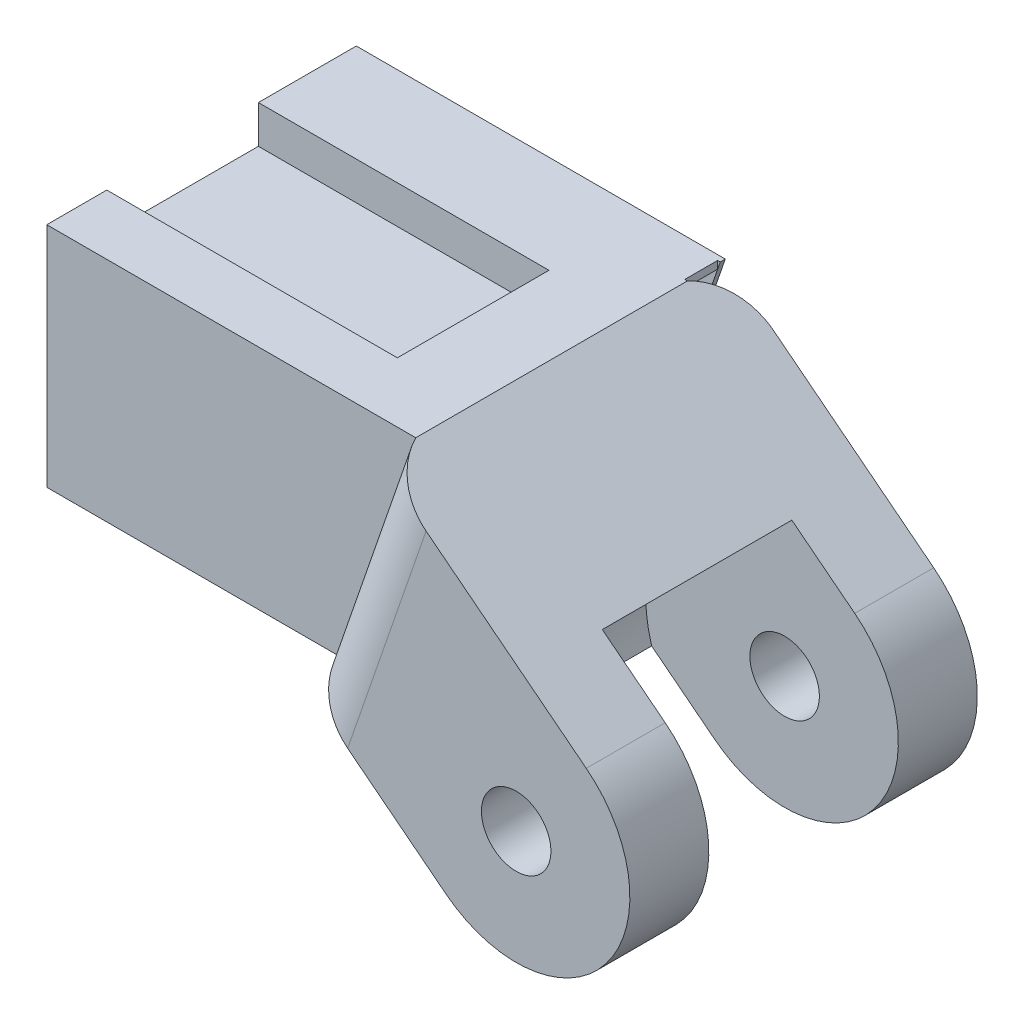
SolidWorks part; units mm, degrees
ref_plane "Front Plane" through (0, 0, 0) normal (0, 0, 1) x (1, 0, 0)
ref_plane "Top Plane" through (0, 0, 0) normal (0, 1, 0) x (1, 0, 0)
ref_plane "Right Plane" through (0, 0, 0) normal (1, 0, 0) x (0, 0, -1)
ref_plane "Plane1" through (0, 0, 10.75) normal (0, 0, 1) x (1, 0, 0)
sketch "Sketch1" plane through (0, 0, 0) normal (0, 0, 1) x (1, 0, 0)
  line L0 (-40.1551, -0.8363) -> (-17.1551, -0.8363)
  line L1 (-17.1551, -0.8363) -> (-5.5478, -9.923)
  line L2 (-40.1551, -0.8363) -> (-40.1551, 17.1637)
  line L3 (-40.1551, 17.1637) -> (-10.9475, 17.1637)
  line L4 (-10.9475, 17.1637) -> (5.5478, 4.2505)
  line L5 (-5.5478, -9.923) -> (5.5478, 4.2505) construction
  arc A1 (-5.5478, -9.923) -> (5.5478, 4.2505) centre (0, -2.8363) ccw
  dimension "D3" = 23
  dimension "D1" = 18
  dimension "D2" = 18
  dimension "D4" = 20
extrude "Boss-Extrude1" add sketch "Sketch1" along normal blind 5
sketch "Sketch14" plane through (0, 0, 5) normal (0, 0, 1) x (1, 0, 0)
  line L0 (-40.1551, -0.8363) -> (-40.1551, 17.1637)
  line L1 (-40.1551, 17.1637) -> (-10.9475, 17.1637)
  line L2 (-5.5478, -9.923) -> (-17.1551, -0.8363)
  line L3 (-10.9475, 17.1637) -> (-40.1551, 17.1637) construction
  line L7 (-17.1551, -0.8363) -> (-40.1551, -0.8363)
  line L8 (-10.9475, 17.1637) -> (5.5478, 4.2505)
  arc A1 (-5.5478, -9.923) -> (5.5478, 4.2505) centre (0, -2.8363) ccw construction
  arc A2 (-5.5478, -9.923) -> (5.5478, 4.2505) centre (0, -2.8363) ccw
extrude "Boss-Extrude7" add sketch "Sketch14" along normal blind 5.75 contours L2 L7 L0 L1 L8 A2
sketch "Sketch27" plane through (0, 0, 0) normal (0, 0, 1) x (1, 0, 0)
  line L0 (-17.1551, -0.8363) -> (-10.9475, 17.1637)
  line L1 (-10.9475, 17.1637) -> (5.5478, 4.2505)
  line L2 (-17.1551, -0.8363) -> (-5.5478, -9.923)
  arc A0 (-5.5478, -9.923) -> (5.5478, 4.2505) centre (0, -2.8363) ccw
  arc A1 (-5.5478, -9.923) -> (5.5478, 4.2505) centre (0, -2.8363) ccw construction
extrude "Boss-Extrude8" add sketch "Sketch27" against normal blind 3
sketch "Sketch15" plane through (0, 0, -3) normal (0, 0, -1) x (-1, 0, 0)
  circle A0 centre (0, -2.8363) radius 2.75
  arc A1 (-5.5478, 4.2505) -> (5.5478, -9.923) centre (0, -2.8363) ccw construction
  dimension "D1" = 5.5
extrude "Cut-Extrude7" cut sketch "Sketch15" against normal through all
fillet "Fillet2" radius 5 1 edges at (-14.0513, 8.1637, -3)
mirror "Mirror1" about plane through (0, -2.8363, 10.75) normal (0, 0, 1) of bodies 117 114
sketch "Sketch16" plane through (-40.1551, 0, 0) normal (-1, 0, 0) x (0, 0, 1)
  line L0 (21.5, -0.8363) -> (0, -0.8363) construction
  line L1 (4.75, -0.8363) -> (16.75, -0.8363)
  line L2 (4.75, -0.8363) -> (4.75, 2.1637)
  line L3 (4.75, 2.1637) -> (16.75, 2.1637)
  line L4 (16.75, -0.8363) -> (16.75, 2.1637)
  line L6 (21.5, 17.1637) -> (0, 17.1637) construction
  line L8 (16.75, 17.1637) -> (4.75, 17.1637)
  line L9 (16.75, 17.1637) -> (16.75, 14.1637)
  line L11 (16.75, 14.1637) -> (4.75, 14.1637)
  line L12 (4.75, 17.1637) -> (4.75, 14.1637)
  point P7 (10.75, 17.1637)
  dimension "D1" = 12
  dimension "D2" = 3
extrude "Cut-Extrude8" cut sketch "Sketch16" against normal blind 23
sketch "Sketch17" plane through (-40.1551, 0, 0) normal (-1, 0, 0) x (0, 0, 1)
  line L0 (21.5, -0.8363) -> (16.75, -0.8363) construction
  line L1 (21.5, 17.1637) -> (21.5, -0.8363) construction
  circle A0 centre (10.75, 8.1637) radius 2.35
  dimension "D1" = 4.7
  dimension "D2" = 9
  dimension "D3" = 10.75
extrude "Cut-Extrude9" cut sketch "Sketch17" against normal blind 32
sketch "Sketch20" plane through (-40.1551, 0, 0) normal (-1, 0, 0) x (0, 0, 1)
  line L0 (14.5, 5.9987) -> (14.5, 2.1637)
  line L1 (10.75, 3.8336) -> (14.5, 5.9987) construction
  line L2 (14.5, 5.9987) -> (14.5, 10.3288)
  line L3 (14.5, 10.3288) -> (10.75, 12.4939)
  line L4 (10.75, 12.4939) -> (7, 10.3288)
  line L5 (7, 10.3288) -> (7, 5.9987)
  line L6 (7, 5.9987) -> (10.75, 3.8336) construction
  line L9 (16.75, 2.1637) -> (4.75, 2.1637) construction
  line L10 (14.5, 2.1637) -> (7, 2.1637)
  line L11 (7, 2.1637) -> (7, 5.9987)
  circle A0 centre (10.75, 8.1637) radius 3.75 construction
  dimension "D1" = 7.5
extrude "Cut-Extrude11" cut sketch "Sketch20" against normal blind 3.8 from offset 8 offset against normal yes
pattern_linear "LPattern1" count 2 spacing 10 along (1, 0, 0) of "Cut-Extrude11"
sketch "Sketch26" plane through (0, 0, 10.75) normal (0, 0, 1) x (1, 0, 0)
  circle A0 centre (0, -2.8363) radius 11
extrude "Cut-Extrude12" cut sketch "Sketch26" against normal mid plane 15
sketch "Sketch28" plane through (0, 0, -3) normal (0, 0, -1) x (-1, 0, 0)
  line L0 (40.1551, 17.1637) -> (40.1551, -0.8363) construction
  line L1 (40.1551, 17.1637) -> (11.1544, 17.1637)
  line L2 (40.1551, 17.1637) -> (40.1551, 16.5637)
  line L3 (40.1551, 16.5637) -> (11.1544, 16.5637)
  line L4 (11.1544, 17.1637) -> (11.1544, 16.5637)
  line L5 (40.1551, -0.8363) -> (17.1551, -0.8363)
  line L6 (40.1551, -0.8363) -> (40.1551, -0.2363)
  line L7 (40.1551, -0.2363) -> (17.1551, -0.2363)
  line L8 (17.1551, -0.8363) -> (17.1551, -0.2363)
  line L9 (40.1551, 11.6637) -> (13.0512, 11.6637)
  line L10 (40.1551, 11.6637) -> (40.1551, 11.0637)
  line L11 (40.1551, 11.0637) -> (13.0512, 11.0637)
  line L12 (13.0512, 11.6637) -> (13.0512, 11.0637)
  line L13 (10.9475, 17.1637) -> (17.1551, -0.8363) construction
  line L14 (40.1551, 6.1637) -> (14.948, 6.1637)
  line L15 (40.1551, 6.1637) -> (40.1551, 5.5637)
  line L16 (40.1551, 5.5637) -> (14.948, 5.5637)
  line L17 (14.948, 6.1637) -> (14.948, 5.5637)
  line L18 (13.3382, -3.8243) -> (17.1551, -0.8363) construction
  point P20 (13.1202, 10.8637)
  point P23 (11.2234, 16.3637)
  point P24 (15.017, 5.3637)
  point P25 (17.1494, -0.8408)
  dimension "D1" = 0.6
  dimension "D2" = 5.5
  dimension "D3" = 5.5
extrude "Boss-Extrude9" add sketch "Sketch28" against normal blind 3
sketch "Sketch29" plane through (0, 0, -3) normal (0, 0, -1) x (-1, 0, 0)
  line L0 (40.1551, 17.1637) -> (40.1551, -0.8363)
  line L1 (40.1551, 17.1637) -> (11.1544, 17.1637) construction
  line L2 (40.1551, 16.5637) -> (40.1551, 17.1637) construction
  line L3 (40.1551, -0.8363) -> (17.1551, -0.8363)
  line L4 (17.1551, -0.8363) -> (11.1544, 16.5637)
  line L5 (11.1544, 16.5637) -> (10.9475, 17.1637)
  line L6 (10.9475, 17.1637) -> (40.1551, 17.1637)
extrude "Boss-Extrude10" add sketch "Sketch29" against normal blind 0.4 contours L6 L0 L3 L4 L5
